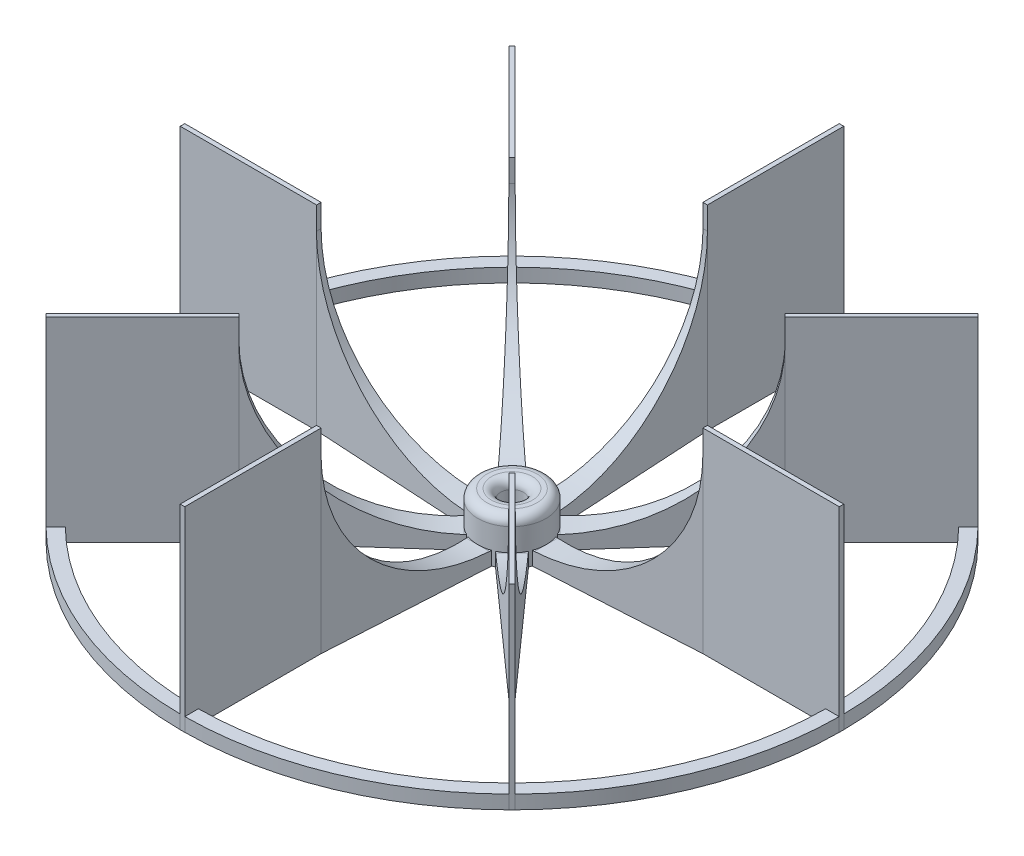
SolidWorks part; units mm, degrees
ref_plane "Front Plane" through (0, 0, 0) normal (0, 0, 1) x (1, 0, 0)
ref_plane "Top Plane" through (0, 0, 0) normal (0, 1, 0) x (1, 0, 0)
ref_plane "Right Plane" through (0, 0, 0) normal (1, 0, 0) x (0, 0, -1)
sketch "Sketch1" plane through (0, 0, 0) normal (0, 1, 0) x (1, 0, 0)
  line L0 (0, 9.525) -> (0, 73.025) construction
  line L1 (-0.635, 53.975) -> (-3.2577, 8.9506)
  line L2 (-0.635, 92.075) -> (0.635, 92.075)
  line L3 (-0.635, 92.075) -> (-0.635, 53.975)
  line L5 (0.635, 92.075) -> (0.635, 53.975)
  line L6 (-0.635, 92.075) -> (0.635, 53.975) construction
  line L7 (-0.635, 53.975) -> (0.635, 92.075) construction
  line L8 (-100, 100) -> (100, 100) construction
  line L9 (-100, 100) -> (-100, -100) construction
  line L10 (-100, -100) -> (100, -100) construction
  line L11 (100, 100) -> (100, -100) construction
  line L12 (-100, 100) -> (100, -100) construction
  line L13 (-100, -100) -> (100, 100) construction
  line L14 (0, 0) -> (-3.2577, 8.9506) construction
  line L15 (0, 0) -> (0, 9.525) construction
  line L16 (0.635, 53.975) -> (3.2577, 8.9506)
  circle A0 centre (0, 0) radius 73.025 construction
  circle A1 centre (0, 0) radius 9.525 construction
  arc A2 (3.2577, 8.9506) -> (-3.2577, 8.9506) centre (0, 0) ccw
  dimension "D1" = 19.05
  dimension "D2" = 146.05
  dimension "D3" = 1.27
  dimension "D4" = 38.1
  dimension "D5" = 200
  dimension "D6" = 200
  dimension "D7" = 20
extrude "Boss-Extrude1" add sketch "Sketch1" along normal blind 3.81
sketch "Sketch2" plane through (0, 3.81, 0) normal (0, 1, 0) x (1, 0, 0)
  line L1 (-0.635, 92.075) -> (0.635, 92.075)
  line L2 (-0.635, 92.075) -> (-0.635, 53.975)
  line L3 (-0.635, 53.975) -> (0.635, 53.975)
  line L4 (0.635, 92.075) -> (0.635, 53.975)
extrude "Boss-Extrude2" add sketch "Sketch2" along normal blind 50.8
fillet "Fillet1" radius 44.45 1 edges at (0, 3.81, -53.975)
sketch "Sketch3" plane through (0, 0, 0) normal (1, 0, 0) x (0, 0, -1)
  line L0 (0, 0) -> (0, 50000) construction
sketch "Sketch4" plane through (0, 0, 0) normal (0, 1, 0) x (1, 0, 0)
  circle A0 centre (0, 0) radius 3.175
  circle A1 centre (0, 0) radius 9.525
  arc A2 (0, 9.525) -> (-3.2577, 8.9506) centre (0, 0) ccw construction
  dimension "D1" = 6.35
extrude "Boss-Extrude3" add sketch "Sketch4" along normal blind 12.7
pattern_circular "CirPattern5" count 8 over 360 about axis through (0, 0, 0) along (0, 1, 0) of "Boss-Extrude1", "Boss-Extrude2", "Fillet1"
sketch "Sketch5" plane through (0, 0, 0) normal (0, 1, 0) x (1, 0, 0)
  line L0 (0.635, 92.075) -> (-0.635, 92.075) construction
  circle A0 centre (0, 0) radius 92.075
  circle A1 centre (0, 0) radius 88.265
  point P5 (0, 92.075)
  dimension "D1" = 3.81
extrude "Boss-Extrude4" add sketch "Sketch5" along normal blind 3.81
fillet "Fillet2" radius 2.54 2 edges at (0, 12.7, 3.175) (0, 12.7, 9.525)
